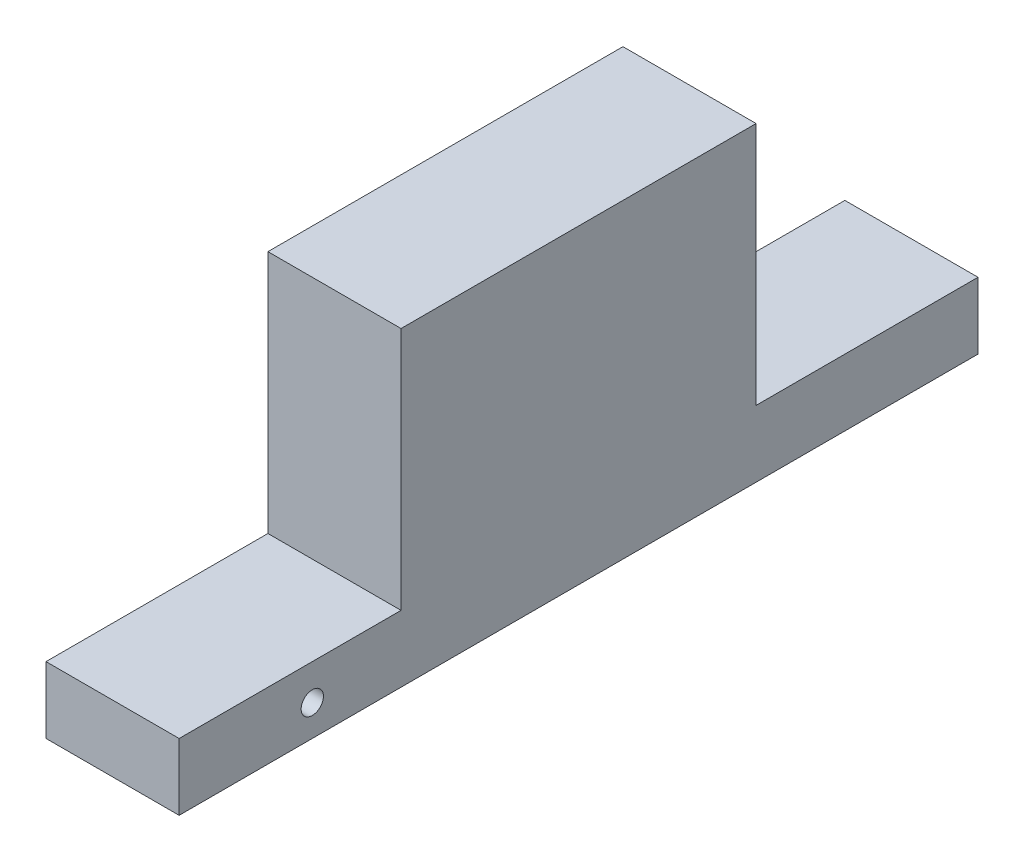
SolidWorks part; units mm, degrees
ref_plane "xy_plane" through (0, 0, 0) normal (0, 0, 1) x (1, 0, 0)
ref_plane "zx_plane" through (0, 0, 0) normal (0, 1, 0) x (1, 0, 0)
ref_plane "yz_plane" through (0, 0, 0) normal (1, 0, 0) x (0, 0, -1)
ref_axis "x_axis" through (-80.9, 0, 0) along (1, 0, 0)
ref_axis "y_axis" through (0, -50, 0) along (0, 1, 0)
ref_axis "z_axis" through (0, 0, -80.9) along (0, 0, 1)
ref_plane "xMid_plane" through (0, 0, 0) normal (1, 0, 0) x (0, 0, -1)
ref_plane "xMin_plane" through (-15, 0, 0) normal (1, 0, 0) x (0, 0, -1)
ref_plane "xMax_plane" through (15, 0, 0) normal (1, 0, 0) x (0, 0, -1)
ref_plane "yMid_plane" through (0, 0, 0) normal (0, 1, 0) x (1, 0, 0)
ref_plane "yMin_plane" through (0, -35, 0) normal (0, 1, 0) x (1, 0, 0)
ref_plane "yMax_plane" through (0, 35, 0) normal (0, 1, 0) x (1, 0, 0)
ref_plane "zMid_plane" through (0, 0, 0) normal (0, 0, 1) x (1, 0, 0)
ref_plane "zMin_plane" through (0, 0, -90) normal (0, 0, 1) x (1, 0, 0)
ref_plane "zMax_plane" through (0, 0, 90) normal (0, 0, 1) x (1, 0, 0)
sketch "projectionYz_sketch" plane through (0, 0, 0) normal (1, 0, 0) x (0, 0, -1)
  line L0 (90, -35) -> (90, -20)
  line L1 (90, -20) -> (40, -20)
  line L2 (40, -20) -> (40, 35)
  line L3 (40, 35) -> (-40, 35)
  line L4 (-40, 35) -> (-40, -20)
  line L5 (-40, -20) -> (-90, -20)
  line L6 (-90, -20) -> (-90, -35)
  line L7 (90, -35) -> (-90, -35)
  line L8 (90, 55) -> (90, -55) construction
  line L9 (55, -35) -> (-55, -35) construction
  line L10 (-90, 55) -> (-90, -55) construction
  line L11 (40, 90) -> (40, -20) construction
  line L12 (-40, 90) -> (-40, -20) construction
  line L13 (55, 35) -> (-55, 35) construction
  dimension "D1" = 15
extrude "mainBody_extrude" add sketch "projectionYz_sketch" along normal up to surface (15 mm away) from surface up to plane "xMax_plane" starting at plane "xMin_plane"
sketch "pivotShaftHole_sketch" plane through (0, 0, 0) normal (1, 0, 0) x (0, 0, -1)
  circle A0 centre (-60, -28) radius 2.51
  dimension "D1" = 5.02
extrude "pivotShaftHole_cut" cut sketch "pivotShaftHole_sketch" against normal through all both and the other way through all from surface starting at plane "xMid_plane"
equation "\"D1@xMin_plane\" = \"externalParameters.this.extent.x\" / 2"
equation "\"D1@xMax_plane\" = \"externalParameters.this.extent.x\" / 2"
equation "\"D1@yMin_plane\" = \"externalParameters.this.extent.y\" / 2"
equation "\"D1@yMax_plane\"= \"externalParameters.this.extent.y\" / 2"
equation "\"D1@zMin_plane\" = \"externalParameters.this.extent.z\" / 2"
equation "\"D1@zMax_plane\" = \"externalParameters.this.extent.z\" / 2"
equation "\"D1@projectionYz_sketch\" = \"externalParameters.this.foot.extent.y\""
equation "\"D1@pivotShaftHole_sketch\"=\"externalParameters.pivotShaft.holeDiameter\""
